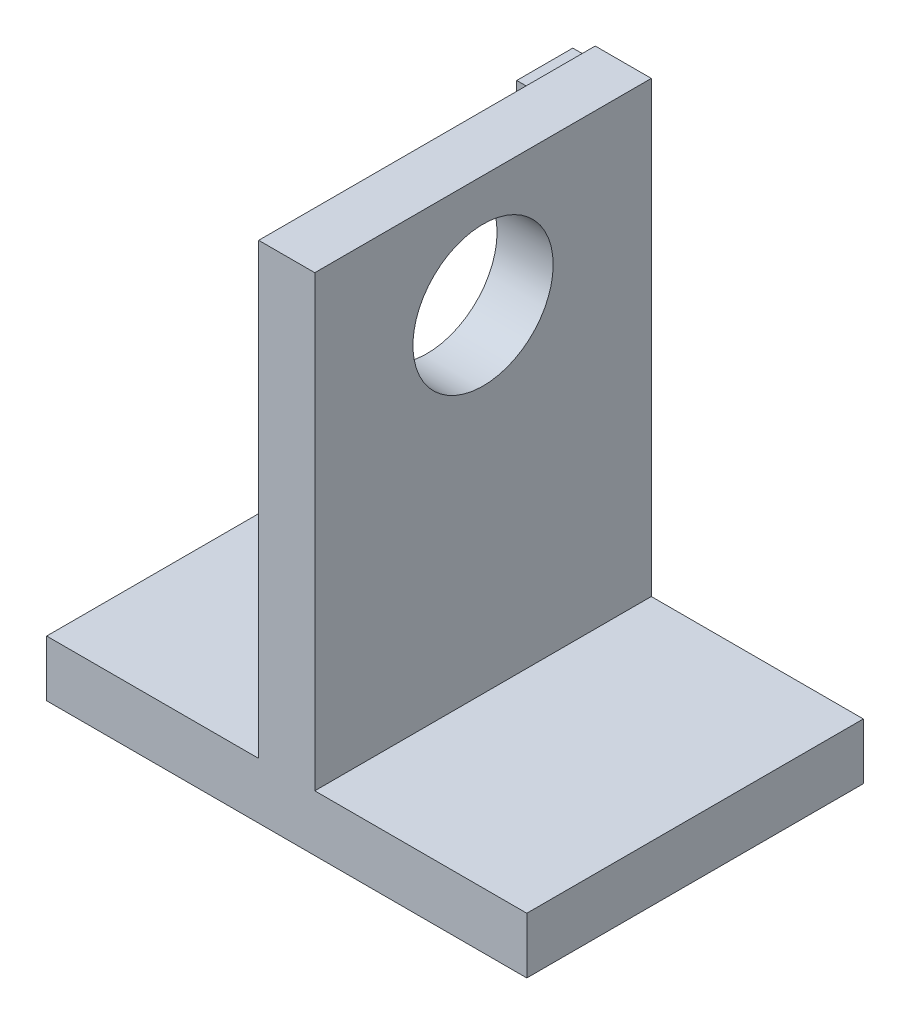
SolidWorks part; units mm, degrees
ref_plane "Front Plane" through (0, 0, 0) normal (0, 0, 1) x (1, 0, 0)
ref_plane "Top Plane" through (0, 0, 0) normal (0, 1, 0) x (1, 0, 0)
ref_plane "Right Plane" through (0, 0, 0) normal (1, 0, 0) x (0, 0, -1)
sketch "Sketch1" plane through (0, 0, 0) normal (0, 0, 1) x (1, 0, 0)
  line L0 (-1.397, 3.175) -> (-1.397, 53.975)
  line L1 (-1.397, 53.975) -> (4.953, 53.975)
  line L2 (4.953, 53.975) -> (4.953, 3.175)
  line L3 (4.953, 3.175) -> (28.956, 3.175)
  line L4 (28.956, 3.175) -> (28.956, -3.175)
  line L5 (28.956, -3.175) -> (-25.4, -3.175)
  line L6 (-25.4, -3.175) -> (-25.4, 3.175)
  line L7 (-25.4, 3.175) -> (-1.397, 3.175)
  point P12 (28.956, 0)
  dimension "D1" = 6.35
  dimension "D2" = 6.35
  dimension "D3" = 50.8
  dimension "D4" = 25.4
  dimension "D5" = 24.003
extrude "Boss-Extrude1" add sketch "Sketch1" along normal mid plane 38.1 contours L2 L3 L4 L5 L6 L7 L0 L1
sketch "Sketch2" plane through (4.953, 0, 0) normal (1, 0, 0) x (0, 0, -1)
  line L1 (-19.05, 28.575) -> (19.05, 28.575) construction
  line L2 (-19.05, 28.575) -> (-19.05, 53.975) construction
  line L3 (-19.05, 53.975) -> (19.05, 53.975)
  line L4 (19.05, 28.575) -> (19.05, 53.975) construction
  line L5 (-19.05, 28.575) -> (19.05, 53.975) construction
  line L6 (-19.05, 53.975) -> (19.05, 28.575) construction
  line L7 (-19.05, 53.975) -> (19.05, 53.975) construction
  line L9 (19.05, 53.975) -> (19.05, 3.175) construction
  line L10 (-19.05, 53.975) -> (-19.05, 3.175) construction
  circle A0 centre (0, 41.275) radius 7.9375
  point P0 (0, 41.275)
  dimension "D2" = 15.875
  dimension "D1" = 25.4
extrude "Cut-Extrude1" cut sketch "Sketch2" against normal through all both and the other way through all contours A0 region at (4.953, 41.275, 0)
sketch "Sketch3" plane through (-1.397, 0, 0) normal (-1, 0, 0) x (0, 0, 1)
  line L0 (-19.05, 3.175) -> (-19.05, 53.975) construction
  line L1 (-19.05, 52.5018) -> (-12.7, 52.5018)
  line L2 (-19.05, 52.5018) -> (-19.05, 38.9382)
  line L3 (-19.05, 38.9382) -> (-12.7, 38.9382)
  line L4 (-12.7, 52.5018) -> (-12.7, 38.9382)
  line L5 (-19.05, 45.2882) -> (-12.7, 46.1518) construction
  line L6 (-19.05, 46.1518) -> (-12.7, 46.1518)
  line L7 (-19.05, 46.1518) -> (-19.05, 45.2882)
  line L8 (-19.05, 45.2882) -> (-12.7, 45.2882)
  line L9 (-12.7, 46.1518) -> (-12.7, 45.2882)
  line L10 (-12.7, 45.2882) -> (-19.05, 46.1518) construction
  line L11 (-19.05, 52.5018) -> (-12.7, 38.9382) construction
  line L12 (-12.7, 52.5018) -> (-19.05, 38.9382) construction
  line L13 (19.05, 53.975) -> (-19.05, 53.975) construction
  point P10 (-15.875, 45.72)
  point P11 (-15.875, 45.72)
  line M14 (-19.05, 53.975) -> (-19.05, 3.175)
  dimension "D1" = 8.255
  dimension "D2" = 0.8636
  dimension "D3" = 6.35
  dimension "D4" = 6.35
extrude "Boss-Extrude2" add sketch "Sketch3" along normal blind 2.54 contours L6 L4 L1 M14 | L8 L3 L4 M14 region at (-1.397, 49.3268, -15.875) region at (-1.397, 42.1132, -15.875)
fillet "Fillet1" radius 6.35 1 edges at (-1.397, 38.9382, -15.875)
sketch "Sketch4" plane through (-1.397, 0, 0) normal (-1, 0, 0) x (0, 0, 1)
  line L1 (-19.05, 46.1518) -> (-12.7, 46.1518)
  line L2 (-19.05, 46.1518) -> (-19.05, 45.2882)
  line L3 (-19.05, 45.2882) -> (-12.7, 45.2882)
  line L4 (-12.7, 46.1518) -> (-12.7, 45.2882)
extrude "Boss-Extrude3" add sketch "Sketch4" along normal blind 1.016
